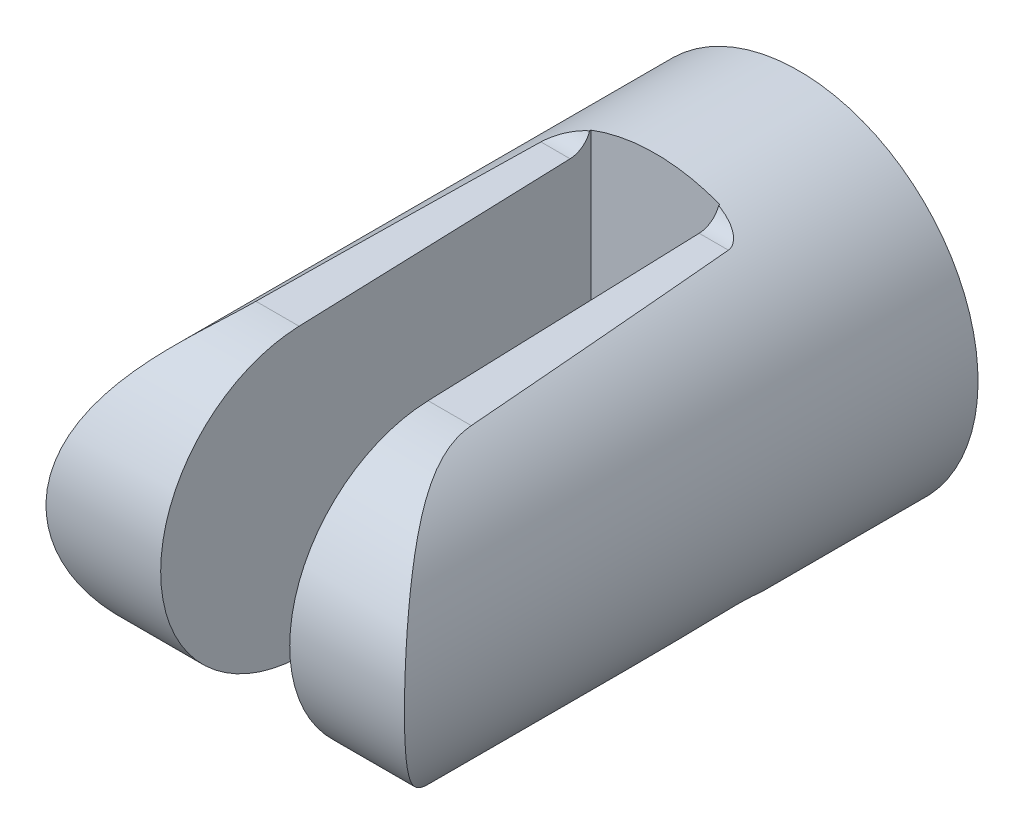
SolidWorks part; units mm, degrees
ref_plane "Front Plane" through (0, 0, 0) normal (0, 0, 1) x (1, 0, 0)
ref_plane "Top Plane" through (0, 0, 0) normal (0, 1, 0) x (1, 0, 0)
ref_plane "Right Plane" through (0, 0, 0) normal (1, 0, 0) x (0, 0, -1)
sketch "Sketch9" plane through (0, 0, 0) normal (0, 1, 0) x (1, 0, 0)
  circle A0 centre (0, 0) radius 125
  dimension "D1" = 250
extrude "Boss-Extrude4" add sketch "Sketch9" along normal blind 100
ref_plane "Plane3" through (45, 0, 0) normal (1, 0, 0) x (0, 0, -1)
sketch "Sketch10" plane through (45, 0, 0) normal (1, 0, 0) x (0, 0, -1)
  line L0 (-99.0268, 286.0827) -> (-72.8746, 100)
  line L1 (125, 100) -> (-125, 100) construction
  line L2 (99.9391, 303.4899) -> (107.0451, 100)
  line L3 (-72.8746, 100) -> (107.0451, 100)
  arc A0 (99.9391, 303.4899) -> (-99.0268, 286.0827) centre (0, 300) ccw
  dimension "D1" = 200
  dimension "D2" = 300
  dimension "D3" = 98
  dimension "D4" = 88
extrude "Boss-Extrude5" add sketch "Sketch10" along normal up to surface (19.5472 mm away) up to face at (0, 100, 125)
fillet "Fillet3" radius 40 1 edges at (73.2797, 100, 72.8746)
fillet "Fillet4" radius 15 1 edges at (54.7736, 100, -107.0451)
mirror "Mirror6" about plane through (0, 0, 0) normal (1, 0, 0) of "Boss-Extrude5", "Fillet3", "Fillet4"
move or copy body "Body-Move/Copy2" bodies to move or copy 110 copy no rotation origin (0, 0, 0) rotation axis (1, 0, 0) rotation angle 90
